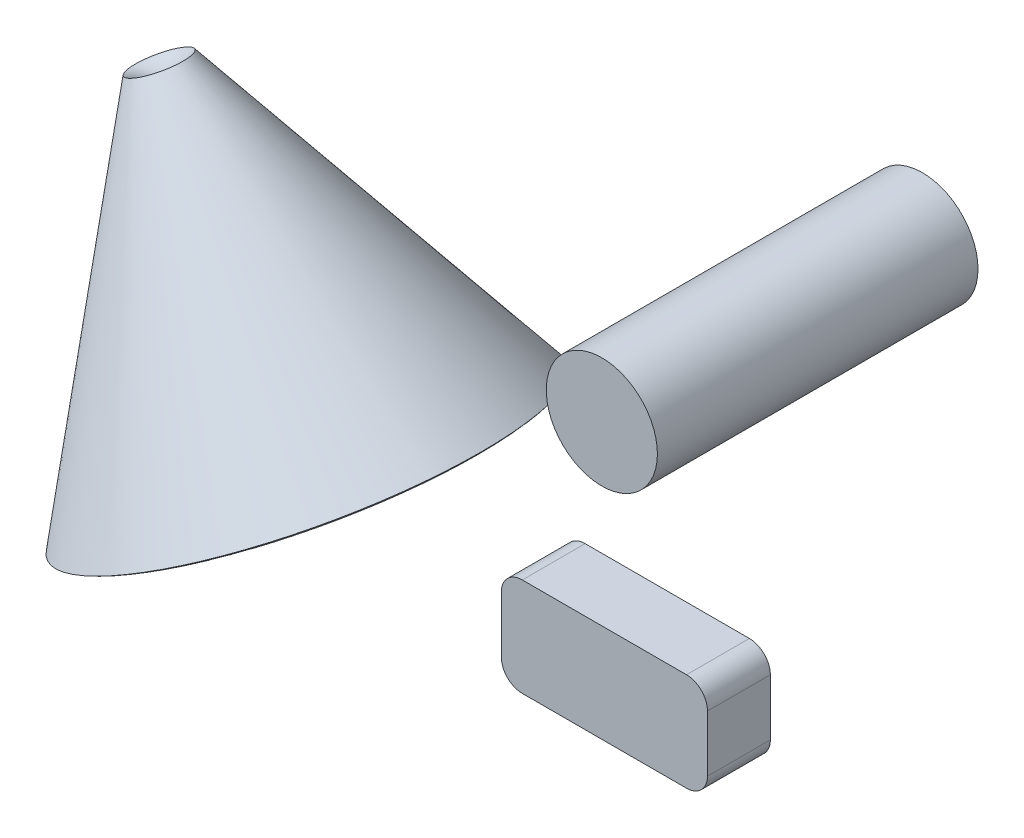
SolidWorks part; units mm, degrees
ref_plane "Front Plane" through (0, 0, 0) normal (0, 0, 1) x (1, 0, 0)
ref_plane "Top Plane" through (0, 0, 0) normal (0, 1, 0) x (1, 0, 0)
ref_plane "Right Plane" through (0, 0, 0) normal (1, 0, 0) x (0, 0, -1)
sketch "Sketch1" plane through (0, 0, 0) normal (0, 0, 1) x (1, 0, 0)
  line L0 (179.6792, 84.1486) -> (179.6792, 252.698)
  line L1 (194.4533, 252.698) -> (287.1043, 84.1486) construction
revolve "Revolve-Thin1" add sketch "Sketch1" angle 360 about L1
fillet "Fillet1" radius 10 2 edges at (189.6792, 252.698, 0) (189.6792, 84.1486, 0)
sketch "Sketch2" plane through (0, 0, 0) normal (0, 0, 1) x (1, 0, 0)
  circle A0 centre (402.2939, 216.0767) radius 26.5216
extrude "Boss-Extrude1" add sketch "Sketch2" against normal blind 153 separate body
sketch "Sketch3" plane through (0, 0, 0) normal (0, 0, 1) x (1, 0, 0)
  line L1 (394.3308, 161.7895) -> (472.719, 161.7895)
  line L2 (384.3308, 151.7895) -> (384.3308, 124.8835)
  line L3 (394.3308, 114.8835) -> (472.719, 114.8835)
  line L4 (482.719, 151.7895) -> (482.719, 124.8835)
  arc A0 (384.3308, 124.8835) -> (394.3308, 114.8835) centre (394.3308, 124.8835) ccw
  arc A1 (472.719, 114.8835) -> (482.719, 124.8835) centre (472.719, 124.8835) ccw
  arc A2 (472.719, 161.7895) -> (482.719, 151.7895) centre (472.719, 151.7895) cw
  arc A3 (394.3308, 161.7895) -> (384.3308, 151.7895) centre (394.3308, 151.7895) ccw
  dimension "D1" = 10
extrude "Boss-Extrude2" add sketch "Sketch3" along normal blind 30 separate body
